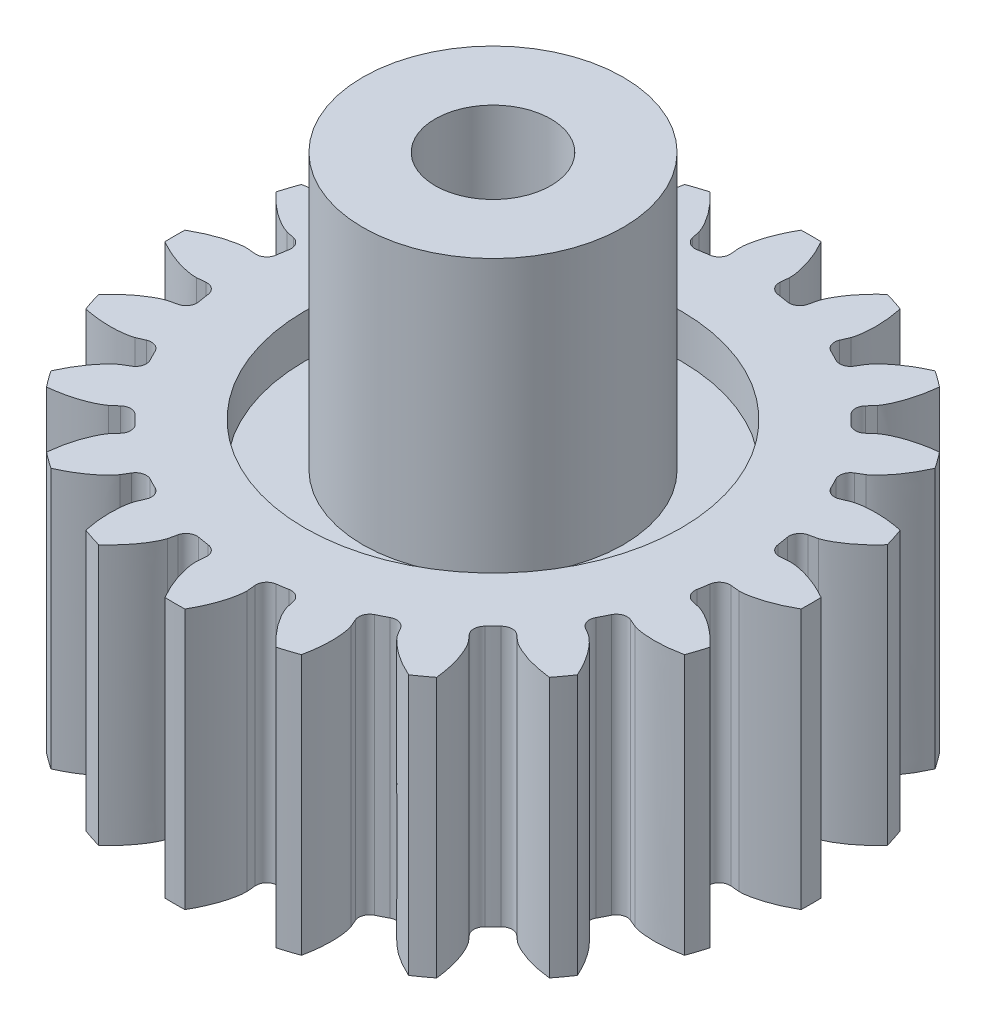
SolidWorks part; units mm, degrees
ref_plane "Front Plane" through (0, 0, 0) normal (0, 0, 1) x (1, 0, 0)
ref_plane "Top Plane" through (0, 0, 0) normal (0, 1, 0) x (1, 0, 0)
ref_plane "Right Plane" through (0, 0, 0) normal (1, 0, 0) x (0, 0, -1)
sketch "Sketch1" plane through (0, 0, 9) normal (0, -1, 0) x (1, 0, 0)
  line L0 (9.0775, -9.8507) -> (9.3734, -9.8777)
  line L1 (9.3734, -8.1223) -> (9.0775, -8.1493)
  line L2 (8.8961, -7.004) -> (9.1858, -6.9382)
  line L3 (8.6434, -5.2687) -> (8.3703, -5.3858)
  line L4 (7.8439, -4.3526) -> (8.0991, -4.2006)
  line L5 (7.0673, -2.7804) -> (6.8438, -2.9761)
  line L6 (6.0239, -2.1562) -> (6.2196, -1.9327)
  line L7 (4.7994, -0.9009) -> (4.6474, -1.1561)
  line L8 (3.6142, -0.6297) -> (3.7313, -0.3566)
  line L9 (2.0618, 0.1858) -> (1.996, -0.1039)
  line L10 (0.8507, 0.0775) -> (0.8777, 0.3734)
  line L11 (-0.8777, 0.3734) -> (-0.8507, 0.0775)
  line L12 (-1.996, -0.1039) -> (-2.0618, 0.1858)
  line L13 (-3.7313, -0.3566) -> (-3.6142, -0.6297)
  line L14 (-4.6474, -1.1561) -> (-4.7994, -0.9009)
  line L15 (-6.2196, -1.9327) -> (-6.0239, -2.1562)
  line L16 (-6.8438, -2.9761) -> (-7.0673, -2.7804)
  line L17 (-8.0991, -4.2006) -> (-7.8439, -4.3526)
  line L18 (-8.3703, -5.3858) -> (-8.6434, -5.2687)
  line L19 (-9.1858, -6.9382) -> (-8.8961, -7.004)
  line L20 (-9.0775, -8.1493) -> (-9.3734, -8.1223)
  line L21 (-9.3734, -9.8777) -> (-9.0775, -9.8507)
  line L22 (-8.8961, -10.996) -> (-9.1858, -11.0618)
  line L23 (-8.6434, -12.7313) -> (-8.3703, -12.6142)
  line L24 (-7.8439, -13.6474) -> (-8.0991, -13.7994)
  line L25 (-7.0673, -15.2196) -> (-6.8438, -15.0239)
  line L26 (-6.0239, -15.8438) -> (-6.2196, -16.0673)
  line L27 (-4.7994, -17.0991) -> (-4.6474, -16.8439)
  line L28 (-3.6142, -17.3703) -> (-3.7313, -17.6434)
  line L29 (-2.0618, -18.1858) -> (-1.996, -17.8961)
  line L30 (-0.8507, -18.0775) -> (-0.8777, -18.3734)
  line L31 (0.8777, -18.3734) -> (0.8507, -18.0775)
  line L32 (1.996, -17.8961) -> (2.0618, -18.1858)
  line L33 (3.7313, -17.6434) -> (3.6142, -17.3703)
  line L34 (4.6474, -16.8439) -> (4.7994, -17.0991)
  line L35 (6.2196, -16.0673) -> (6.0239, -15.8438)
  line L36 (6.8438, -15.0239) -> (7.0673, -15.2196)
  line L37 (8.0991, -13.7994) -> (7.8439, -13.6474)
  line L38 (8.3703, -12.6142) -> (8.6434, -12.7313)
  line L39 (9.1858, -11.0618) -> (8.8961, -10.996)
  arc A0 (8.6092, -10.5634) -> (8.671, -10.1735) centre (0, -9) ccw
  arc A1 (8.671, -10.1735) -> (9.0775, -9.8507) centre (9.0425, -10.2241) cw
  arc A2 (10.9945, -9.3464) -> (10.9945, -8.6536) centre (-0.0001, -9) ccw
  arc A3 (9.0775, -8.1493) -> (8.671, -7.8265) centre (9.0425, -7.7759) cw
  arc A4 (8.671, -7.8265) -> (8.6092, -7.4366) centre (0, -9) ccw
  arc A5 (8.6092, -7.4366) -> (8.8961, -7.004) centre (8.9782, -7.3699) cw
  arc A6 (10.5634, -5.932) -> (10.3493, -5.273) centre (-0.0001, -9) ccw
  arc A7 (8.3703, -5.3858) -> (7.8839, -5.2045) centre (8.2217, -5.0415) cw
  arc A8 (7.8839, -5.2045) -> (7.7047, -4.8527) centre (0, -9) ccw
  arc A9 (7.7047, -4.8527) -> (7.8439, -4.3526) centre (8.0351, -4.6752) cw
  arc A10 (9.0983, -2.8179) -> (8.6911, -2.2573) centre (-0.0001, -9) ccw
  arc A11 (6.8438, -2.9761) -> (6.3252, -2.954) centre (6.5961, -2.6946) cw
  arc A12 (6.3252, -2.954) -> (6.046, -2.6748) centre (0, -9) ccw
  arc A13 (6.046, -2.6748) -> (6.0239, -2.1562) centre (6.3054, -2.4039) cw
  arc A14 (6.7427, -0.3089) -> (6.1821, 0.0983) centre (0, -9.0001) ccw
  arc A15 (4.6474, -1.1561) -> (4.1473, -1.2953) centre (4.3248, -0.9649) cw
  arc A16 (4.1473, -1.2953) -> (3.7955, -1.1161) centre (0, -9) ccw
  arc A17 (3.7955, -1.1161) -> (3.6142, -0.6297) centre (3.9585, -0.7783) cw
  arc A18 (3.727, 1.3493) -> (3.068, 1.5634) centre (0, -9.0001) ccw
  arc A19 (1.996, -0.1039) -> (1.5634, -0.3908) centre (1.6301, -0.0218) cw
  arc A20 (1.5634, -0.3908) -> (1.1735, -0.329) centre (0, -9) ccw
  arc A21 (1.1735, -0.329) -> (0.8507, 0.0775) centre (1.2241, 0.0425) cw
  arc A22 (0.3464, 1.9945) -> (-0.3464, 1.9945) centre (0, -9.0001) ccw
  arc A23 (-0.8507, 0.0775) -> (-1.1735, -0.329) centre (-1.2241, 0.0425) cw
  arc A24 (-1.1735, -0.329) -> (-1.5634, -0.3908) centre (0, -9) ccw
  arc A25 (-1.5634, -0.3908) -> (-1.996, -0.1039) centre (-1.6301, -0.0218) cw
  arc A26 (-3.068, 1.5634) -> (-3.727, 1.3493) centre (0, -9.0001) ccw
  arc A27 (-3.6142, -0.6297) -> (-3.7955, -1.1161) centre (-3.9585, -0.7783) cw
  arc A28 (-3.7955, -1.1161) -> (-4.1473, -1.2953) centre (0, -9) ccw
  arc A29 (-4.1473, -1.2953) -> (-4.6474, -1.1561) centre (-4.3248, -0.9649) cw
  arc A30 (-6.1821, 0.0983) -> (-6.7427, -0.3089) centre (0, -9.0001) ccw
  arc A31 (-6.0239, -2.1562) -> (-6.046, -2.6748) centre (-6.3054, -2.4039) cw
  arc A32 (-6.046, -2.6748) -> (-6.3252, -2.954) centre (0, -9) ccw
  arc A33 (-6.3252, -2.954) -> (-6.8438, -2.9761) centre (-6.5961, -2.6946) cw
  arc A34 (-8.6911, -2.2573) -> (-9.0983, -2.8179) centre (0.0001, -9) ccw
  arc A35 (-7.8439, -4.3526) -> (-7.7047, -4.8527) centre (-8.0351, -4.6752) cw
  arc A36 (-7.7047, -4.8527) -> (-7.8839, -5.2045) centre (0, -9) ccw
  arc A37 (-7.8839, -5.2045) -> (-8.3703, -5.3858) centre (-8.2217, -5.0415) cw
  arc A38 (-10.3493, -5.273) -> (-10.5634, -5.932) centre (0.0001, -9) ccw
  arc A39 (-8.8961, -7.004) -> (-8.6092, -7.4366) centre (-8.9782, -7.3699) cw
  arc A40 (-8.6092, -7.4366) -> (-8.671, -7.8265) centre (0, -9) ccw
  arc A41 (-8.671, -7.8265) -> (-9.0775, -8.1493) centre (-9.0425, -7.7759) cw
  arc A42 (-10.9945, -8.6536) -> (-10.9945, -9.3464) centre (0.0001, -9) ccw
  arc A43 (-9.0775, -9.8507) -> (-8.671, -10.1735) centre (-9.0425, -10.2241) cw
  arc A44 (-8.671, -10.1735) -> (-8.6092, -10.5634) centre (0, -9) ccw
  arc A45 (-8.6092, -10.5634) -> (-8.8961, -10.996) centre (-8.9782, -10.6301) cw
  arc A46 (-10.5634, -12.068) -> (-10.3493, -12.727) centre (0.0001, -9) ccw
  arc A47 (-8.3703, -12.6142) -> (-7.8839, -12.7955) centre (-8.2217, -12.9585) cw
  arc A48 (-7.8839, -12.7955) -> (-7.7047, -13.1473) centre (0, -9) ccw
  arc A49 (-7.7047, -13.1473) -> (-7.8439, -13.6474) centre (-8.0351, -13.3248) cw
  arc A50 (-9.0983, -15.1821) -> (-8.6911, -15.7427) centre (0.0001, -9) ccw
  arc A51 (-6.8438, -15.0239) -> (-6.3252, -15.046) centre (-6.5961, -15.3054) cw
  arc A52 (-6.3252, -15.046) -> (-6.046, -15.3252) centre (0, -9) ccw
  arc A53 (-6.046, -15.3252) -> (-6.0239, -15.8438) centre (-6.3054, -15.5961) cw
  arc A54 (-6.7427, -17.6911) -> (-6.1821, -18.0983) centre (0, -8.9999) ccw
  arc A55 (-4.6474, -16.8439) -> (-4.1473, -16.7047) centre (-4.3248, -17.0351) cw
  arc A56 (-4.1473, -16.7047) -> (-3.7955, -16.8839) centre (0, -9) ccw
  arc A57 (-3.7955, -16.8839) -> (-3.6142, -17.3703) centre (-3.9585, -17.2217) cw
  arc A58 (-3.727, -19.3493) -> (-3.068, -19.5634) centre (0, -8.9999) ccw
  arc A59 (-1.996, -17.8961) -> (-1.5634, -17.6092) centre (-1.6301, -17.9782) cw
  arc A60 (-1.5634, -17.6092) -> (-1.1735, -17.671) centre (0, -9) ccw
  arc A61 (-1.1735, -17.671) -> (-0.8507, -18.0775) centre (-1.2241, -18.0425) cw
  arc A62 (-0.3464, -19.9945) -> (0.3464, -19.9945) centre (0, -8.9999) ccw
  arc A63 (0.8507, -18.0775) -> (1.1735, -17.671) centre (1.2241, -18.0425) cw
  arc A64 (1.1735, -17.671) -> (1.5634, -17.6092) centre (0, -9) ccw
  arc A65 (1.5634, -17.6092) -> (1.996, -17.8961) centre (1.6301, -17.9782) cw
  arc A66 (3.068, -19.5634) -> (3.727, -19.3493) centre (0, -8.9999) ccw
  arc A67 (3.6142, -17.3703) -> (3.7955, -16.8839) centre (3.9585, -17.2217) cw
  arc A68 (3.7955, -16.8839) -> (4.1473, -16.7047) centre (0, -9) ccw
  arc A69 (4.1473, -16.7047) -> (4.6474, -16.8439) centre (4.3248, -17.0351) cw
  arc A70 (6.1821, -18.0983) -> (6.7427, -17.6911) centre (0, -8.9999) ccw
  arc A71 (6.0239, -15.8438) -> (6.046, -15.3252) centre (6.3054, -15.5961) cw
  arc A72 (6.046, -15.3252) -> (6.3252, -15.046) centre (0, -9) ccw
  arc A73 (6.3252, -15.046) -> (6.8438, -15.0239) centre (6.5961, -15.3054) cw
  arc A74 (8.6911, -15.7427) -> (9.0983, -15.1821) centre (-0.0001, -9) ccw
  arc A75 (7.8439, -13.6474) -> (7.7047, -13.1473) centre (8.0351, -13.3248) cw
  arc A76 (7.7047, -13.1473) -> (7.8839, -12.7955) centre (0, -9) ccw
  arc A77 (7.8839, -12.7955) -> (8.3703, -12.6142) centre (8.2217, -12.9585) cw
  arc A78 (10.3493, -12.727) -> (10.5634, -12.068) centre (-0.0001, -9) ccw
  arc A79 (8.8961, -10.996) -> (8.6092, -10.5634) centre (8.9782, -10.6301) cw
  spline S0 degree 3 poles (9.3734, -9.8777) (9.5088, -9.8801) (9.6445, -9.8584) (9.7771, -9.8308) (9.9887, -9.7868) (10.1959, -9.7199) (10.3963, -9.6391) (10.6021, -9.556) (10.802, -9.4571) (10.9945, -9.3464) knots 0 0 0 0 0.000406 0.000406 0.000406 0.001055 0.001055 0.001055 0.001721 0.001721 0.001721 0.001721
  spline S1 degree 3 poles (10.9945, -8.6536) (10.7523, -8.5143) (10.4979, -8.3933) (10.2347, -8.2995) (10.0978, -8.2507) (9.9579, -8.2091) (9.8159, -8.1775) (9.6708, -8.1453) (9.522, -8.1197) (9.3734, -8.1223) knots 0 0 0 0 0.000838 0.000838 0.000838 0.001273 0.001273 0.001273 0.001719 0.001719 0.001719 0.001719
  spline S2 degree 3 poles (9.1858, -6.9382) (9.3154, -6.8986) (9.4377, -6.8361) (9.5554, -6.7689) (9.7429, -6.6616) (9.9194, -6.534) (10.085, -6.3952) (10.255, -6.2525) (10.4146, -6.0967) (10.5634, -5.932) knots 0 0 0 0 0.000406 0.000406 0.000406 0.001055 0.001055 0.001055 0.001721 0.001721 0.001721 0.001721
  spline S3 degree 3 poles (10.3493, -5.273) (10.0759, -5.2154) (9.7966, -5.179) (9.5174, -5.1711) (9.372, -5.167) (9.2261, -5.1706) (9.0814, -5.1845) (8.9334, -5.1987) (8.7839, -5.2203) (8.6434, -5.2687) knots 0 0 0 0 0.000838 0.000838 0.000838 0.001273 0.001273 0.001273 0.001719 0.001719 0.001719 0.001719
  spline S4 degree 3 poles (8.0991, -4.2006) (8.2101, -4.1229) (8.3071, -4.0256) (8.3982, -3.9253) (8.5435, -3.7654) (8.6719, -3.5894) (8.7864, -3.4062) (8.9041, -3.218) (9.0077, -3.0205) (9.0983, -2.8179) knots 0 0 0 0 0.000406 0.000406 0.000406 0.001055 0.001055 0.001055 0.001721 0.001721 0.001721 0.001721
  spline S5 degree 3 poles (8.6911, -2.2573) (8.4133, -2.287) (8.1364, -2.3386) (7.8684, -2.4175) (7.7289, -2.4585) (7.5912, -2.507) (7.4578, -2.5649) (7.3215, -2.6242) (7.186, -2.6909) (7.0673, -2.7804) knots 0 0 0 0 0.000838 0.000838 0.000838 0.001273 0.001273 0.001273 0.001719 0.001719 0.001719 0.001719
  spline S6 degree 3 poles (6.2196, -1.9327) (6.3012, -1.8245) (6.3634, -1.702) (6.419, -1.5785) (6.5077, -1.3815) (6.5755, -1.1745) (6.6278, -0.9649) (6.6816, -0.7495) (6.7191, -0.5296) (6.7427, -0.3089) knots 0 0 0 0 0.000406 0.000406 0.000406 0.001055 0.001055 0.001055 0.001721 0.001721 0.001721 0.001721
  spline S7 degree 3 poles (6.1821, 0.0983) (5.9271, -0.0157) (5.6797, -0.1504) (5.4491, -0.3082) (5.3291, -0.3903) (5.2132, -0.479) (5.1043, -0.5753) (4.9929, -0.6738) (4.8847, -0.7791) (4.7994, -0.9009) knots 0 0 0 0 0.000838 0.000838 0.000838 0.001273 0.001273 0.001273 0.001719 0.001719 0.001719 0.001719
  spline S8 degree 3 poles (3.7313, -0.3566) (3.7754, -0.2285) (3.7967, -0.0928) (3.8115, 0.0419) (3.835, 0.2566) (3.8354, 0.4744) (3.8204, 0.69) (3.805, 0.9114) (3.7727, 1.1321) (3.727, 1.3493) knots 0 0 0 0 0.000406 0.000406 0.000406 0.001055 0.001055 0.001055 0.001721 0.001721 0.001721 0.001721
  spline S9 degree 3 poles (3.068, 1.5634) (2.8607, 1.3761) (2.667, 1.1716) (2.4965, 0.9503) (2.4078, 0.8351) (2.3249, 0.7149) (2.2511, 0.5897) (2.1756, 0.4616) (2.1052, 0.328) (2.0618, 0.1858) knots 0 0 0 0 0.000838 0.000838 0.000838 0.001273 0.001273 0.001273 0.001719 0.001719 0.001719 0.001719
  spline S10 degree 3 poles (0.8777, 0.3734) (0.8801, 0.5088) (0.8584, 0.6445) (0.8308, 0.7771) (0.7868, 0.9887) (0.7199, 1.1959) (0.6391, 1.3963) (0.556, 1.6021) (0.4571, 1.802) (0.3464, 1.9945) knots 0 0 0 0 0.000406 0.000406 0.000406 0.001055 0.001055 0.001055 0.001721 0.001721 0.001721 0.001721
  spline S11 degree 3 poles (-0.3464, 1.9945) (-0.4857, 1.7523) (-0.6067, 1.4979) (-0.7005, 1.2347) (-0.7493, 1.0978) (-0.7909, 0.9579) (-0.8225, 0.8159) (-0.8547, 0.6708) (-0.8803, 0.522) (-0.8777, 0.3734) knots 0 0 0 0 0.000838 0.000838 0.000838 0.001273 0.001273 0.001273 0.001719 0.001719 0.001719 0.001719
  spline S12 degree 3 poles (-2.0618, 0.1858) (-2.1014, 0.3154) (-2.1639, 0.4377) (-2.2311, 0.5554) (-2.3384, 0.7429) (-2.466, 0.9194) (-2.6048, 1.085) (-2.7475, 1.255) (-2.9033, 1.4146) (-3.068, 1.5634) knots 0 0 0 0 0.000406 0.000406 0.000406 0.001055 0.001055 0.001055 0.001721 0.001721 0.001721 0.001721
  spline S13 degree 3 poles (-3.727, 1.3493) (-3.7846, 1.0759) (-3.821, 0.7966) (-3.8289, 0.5174) (-3.833, 0.372) (-3.8294, 0.2261) (-3.8155, 0.0814) (-3.8013, -0.0666) (-3.7797, -0.2161) (-3.7313, -0.3566) knots 0 0 0 0 0.000838 0.000838 0.000838 0.001273 0.001273 0.001273 0.001719 0.001719 0.001719 0.001719
  spline S14 degree 3 poles (-4.7994, -0.9009) (-4.8771, -0.7899) (-4.9744, -0.6929) (-5.0747, -0.6018) (-5.2346, -0.4565) (-5.4106, -0.3281) (-5.5938, -0.2136) (-5.782, -0.0959) (-5.9795, 0.0077) (-6.1821, 0.0983) knots 0 0 0 0 0.000406 0.000406 0.000406 0.001055 0.001055 0.001055 0.001721 0.001721 0.001721 0.001721
  spline S15 degree 3 poles (-6.7427, -0.3089) (-6.713, -0.5867) (-6.6614, -0.8636) (-6.5825, -1.1316) (-6.5415, -1.2711) (-6.493, -1.4088) (-6.4351, -1.5422) (-6.3758, -1.6785) (-6.3091, -1.814) (-6.2196, -1.9327) knots 0 0 0 0 0.000838 0.000838 0.000838 0.001273 0.001273 0.001273 0.001719 0.001719 0.001719 0.001719
  spline S16 degree 3 poles (-7.0673, -2.7804) (-7.1755, -2.6988) (-7.298, -2.6366) (-7.4215, -2.581) (-7.6185, -2.4923) (-7.8255, -2.4245) (-8.0351, -2.3722) (-8.2505, -2.3184) (-8.4704, -2.2809) (-8.6911, -2.2573) knots 0 0 0 0 0.000406 0.000406 0.000406 0.001055 0.001055 0.001055 0.001721 0.001721 0.001721 0.001721
  spline S17 degree 3 poles (-9.0983, -2.8179) (-8.9843, -3.0729) (-8.8496, -3.3203) (-8.6918, -3.5509) (-8.6097, -3.6709) (-8.521, -3.7868) (-8.4247, -3.8957) (-8.3262, -4.0071) (-8.2209, -4.1153) (-8.0991, -4.2006) knots 0 0 0 0 0.000838 0.000838 0.000838 0.001273 0.001273 0.001273 0.001719 0.001719 0.001719 0.001719
  spline S18 degree 3 poles (-8.6434, -5.2687) (-8.7715, -5.2246) (-8.9072, -5.2033) (-9.0419, -5.1885) (-9.2566, -5.165) (-9.4744, -5.1646) (-9.69, -5.1796) (-9.9114, -5.195) (-10.1321, -5.2273) (-10.3493, -5.273) knots 0 0 0 0 0.000406 0.000406 0.000406 0.001055 0.001055 0.001055 0.001721 0.001721 0.001721 0.001721
  spline S19 degree 3 poles (-10.5634, -5.932) (-10.3761, -6.1393) (-10.1716, -6.333) (-9.9503, -6.5035) (-9.8351, -6.5922) (-9.7149, -6.6751) (-9.5897, -6.7489) (-9.4616, -6.8244) (-9.328, -6.8948) (-9.1858, -6.9382) knots 0 0 0 0 0.000838 0.000838 0.000838 0.001273 0.001273 0.001273 0.001719 0.001719 0.001719 0.001719
  spline S20 degree 3 poles (-9.3734, -8.1223) (-9.5088, -8.1199) (-9.6445, -8.1416) (-9.7771, -8.1692) (-9.9887, -8.2132) (-10.1959, -8.2801) (-10.3963, -8.3609) (-10.6021, -8.444) (-10.802, -8.5429) (-10.9945, -8.6536) knots 0 0 0 0 0.000406 0.000406 0.000406 0.001055 0.001055 0.001055 0.001721 0.001721 0.001721 0.001721
  spline S21 degree 3 poles (-10.9945, -9.3464) (-10.7523, -9.4857) (-10.4979, -9.6067) (-10.2347, -9.7005) (-10.0978, -9.7493) (-9.9579, -9.7909) (-9.8159, -9.8225) (-9.6708, -9.8547) (-9.522, -9.8803) (-9.3734, -9.8777) knots 0 0 0 0 0.000838 0.000838 0.000838 0.001273 0.001273 0.001273 0.001719 0.001719 0.001719 0.001719
  spline S22 degree 3 poles (-9.1858, -11.0618) (-9.3154, -11.1014) (-9.4377, -11.1639) (-9.5554, -11.2311) (-9.7429, -11.3384) (-9.9194, -11.466) (-10.085, -11.6048) (-10.255, -11.7475) (-10.4146, -11.9033) (-10.5634, -12.068) knots 0 0 0 0 0.000406 0.000406 0.000406 0.001055 0.001055 0.001055 0.001721 0.001721 0.001721 0.001721
  spline S23 degree 3 poles (-10.3493, -12.727) (-10.0759, -12.7846) (-9.7966, -12.821) (-9.5174, -12.8289) (-9.372, -12.833) (-9.2261, -12.8294) (-9.0814, -12.8155) (-8.9334, -12.8013) (-8.7839, -12.7797) (-8.6434, -12.7313) knots 0 0 0 0 0.000838 0.000838 0.000838 0.001273 0.001273 0.001273 0.001719 0.001719 0.001719 0.001719
  spline S24 degree 3 poles (-8.0991, -13.7994) (-8.2101, -13.8771) (-8.3071, -13.9744) (-8.3982, -14.0747) (-8.5435, -14.2346) (-8.6719, -14.4106) (-8.7864, -14.5938) (-8.9041, -14.782) (-9.0077, -14.9795) (-9.0983, -15.1821) knots 0 0 0 0 0.000406 0.000406 0.000406 0.001055 0.001055 0.001055 0.001721 0.001721 0.001721 0.001721
  spline S25 degree 3 poles (-8.6911, -15.7427) (-8.4133, -15.713) (-8.1364, -15.6614) (-7.8684, -15.5825) (-7.7289, -15.5415) (-7.5912, -15.493) (-7.4578, -15.4351) (-7.3215, -15.3758) (-7.186, -15.3091) (-7.0673, -15.2196) knots 0 0 0 0 0.000838 0.000838 0.000838 0.001273 0.001273 0.001273 0.001719 0.001719 0.001719 0.001719
  spline S26 degree 3 poles (-6.2196, -16.0673) (-6.3012, -16.1755) (-6.3634, -16.298) (-6.419, -16.4215) (-6.5077, -16.6185) (-6.5755, -16.8255) (-6.6278, -17.0351) (-6.6816, -17.2505) (-6.7191, -17.4704) (-6.7427, -17.6911) knots 0 0 0 0 0.000406 0.000406 0.000406 0.001055 0.001055 0.001055 0.001721 0.001721 0.001721 0.001721
  spline S27 degree 3 poles (-6.1821, -18.0983) (-5.9271, -17.9843) (-5.6797, -17.8496) (-5.4491, -17.6918) (-5.3291, -17.6097) (-5.2132, -17.521) (-5.1043, -17.4247) (-4.9929, -17.3262) (-4.8847, -17.2209) (-4.7994, -17.0991) knots 0 0 0 0 0.000838 0.000838 0.000838 0.001273 0.001273 0.001273 0.001719 0.001719 0.001719 0.001719
  spline S28 degree 3 poles (-3.7313, -17.6434) (-3.7754, -17.7715) (-3.7967, -17.9072) (-3.8115, -18.0419) (-3.835, -18.2566) (-3.8354, -18.4744) (-3.8204, -18.69) (-3.805, -18.9114) (-3.7727, -19.1321) (-3.727, -19.3493) knots 0 0 0 0 0.000406 0.000406 0.000406 0.001055 0.001055 0.001055 0.001721 0.001721 0.001721 0.001721
  spline S29 degree 3 poles (-3.068, -19.5634) (-2.8607, -19.3761) (-2.667, -19.1716) (-2.4965, -18.9503) (-2.4078, -18.8351) (-2.3249, -18.7149) (-2.2511, -18.5897) (-2.1756, -18.4616) (-2.1052, -18.328) (-2.0618, -18.1858) knots 0 0 0 0 0.000838 0.000838 0.000838 0.001273 0.001273 0.001273 0.001719 0.001719 0.001719 0.001719
  spline S30 degree 3 poles (-0.8777, -18.3734) (-0.8801, -18.5088) (-0.8584, -18.6445) (-0.8308, -18.7771) (-0.7868, -18.9887) (-0.7199, -19.1959) (-0.6391, -19.3963) (-0.556, -19.6021) (-0.4571, -19.802) (-0.3464, -19.9945) knots 0 0 0 0 0.000406 0.000406 0.000406 0.001055 0.001055 0.001055 0.001721 0.001721 0.001721 0.001721
  spline S31 degree 3 poles (0.3464, -19.9945) (0.4857, -19.7523) (0.6067, -19.4979) (0.7005, -19.2347) (0.7493, -19.0978) (0.7909, -18.9579) (0.8225, -18.8159) (0.8547, -18.6708) (0.8803, -18.522) (0.8777, -18.3734) knots 0 0 0 0 0.000838 0.000838 0.000838 0.001273 0.001273 0.001273 0.001719 0.001719 0.001719 0.001719
  spline S32 degree 3 poles (2.0618, -18.1858) (2.1014, -18.3154) (2.1639, -18.4377) (2.2311, -18.5554) (2.3384, -18.7429) (2.466, -18.9194) (2.6048, -19.085) (2.7475, -19.255) (2.9033, -19.4146) (3.068, -19.5634) knots 0 0 0 0 0.000406 0.000406 0.000406 0.001055 0.001055 0.001055 0.001721 0.001721 0.001721 0.001721
  spline S33 degree 3 poles (3.727, -19.3493) (3.7846, -19.0759) (3.821, -18.7966) (3.8289, -18.5174) (3.833, -18.372) (3.8294, -18.2261) (3.8155, -18.0814) (3.8013, -17.9334) (3.7797, -17.7839) (3.7313, -17.6434) knots 0 0 0 0 0.000838 0.000838 0.000838 0.001273 0.001273 0.001273 0.001719 0.001719 0.001719 0.001719
  spline S34 degree 3 poles (4.7994, -17.0991) (4.8771, -17.2101) (4.9744, -17.3071) (5.0747, -17.3982) (5.2346, -17.5435) (5.4106, -17.6719) (5.5938, -17.7864) (5.782, -17.9041) (5.9795, -18.0077) (6.1821, -18.0983) knots 0 0 0 0 0.000406 0.000406 0.000406 0.001055 0.001055 0.001055 0.001721 0.001721 0.001721 0.001721
  spline S35 degree 3 poles (6.7427, -17.6911) (6.713, -17.4133) (6.6614, -17.1364) (6.5825, -16.8684) (6.5415, -16.7289) (6.493, -16.5912) (6.4351, -16.4578) (6.3758, -16.3215) (6.3091, -16.186) (6.2196, -16.0673) knots 0 0 0 0 0.000838 0.000838 0.000838 0.001273 0.001273 0.001273 0.001719 0.001719 0.001719 0.001719
  spline S36 degree 3 poles (7.0673, -15.2196) (7.1755, -15.3012) (7.298, -15.3634) (7.4215, -15.419) (7.6185, -15.5077) (7.8255, -15.5755) (8.0351, -15.6278) (8.2505, -15.6816) (8.4704, -15.7191) (8.6911, -15.7427) knots 0 0 0 0 0.000406 0.000406 0.000406 0.001055 0.001055 0.001055 0.001721 0.001721 0.001721 0.001721
  spline S37 degree 3 poles (9.0983, -15.1821) (8.9843, -14.9271) (8.8496, -14.6797) (8.6918, -14.4491) (8.6097, -14.3291) (8.521, -14.2132) (8.4247, -14.1043) (8.3262, -13.9929) (8.2209, -13.8847) (8.0991, -13.7994) knots 0 0 0 0 0.000838 0.000838 0.000838 0.001273 0.001273 0.001273 0.001719 0.001719 0.001719 0.001719
  spline S38 degree 3 poles (8.6434, -12.7313) (8.7715, -12.7754) (8.9072, -12.7967) (9.0419, -12.8115) (9.2566, -12.835) (9.4744, -12.8354) (9.69, -12.8204) (9.9114, -12.805) (10.1321, -12.7727) (10.3493, -12.727) knots 0 0 0 0 0.000406 0.000406 0.000406 0.001055 0.001055 0.001055 0.001721 0.001721 0.001721 0.001721
  spline S39 degree 3 poles (10.5634, -12.068) (10.3761, -11.8607) (10.1716, -11.667) (9.9503, -11.4965) (9.8351, -11.4078) (9.7149, -11.3249) (9.5897, -11.2511) (9.4616, -11.1756) (9.328, -11.1052) (9.1858, -11.0618) knots 0 0 0 0 0.000838 0.000838 0.000838 0.001273 0.001273 0.001273 0.001719 0.001719 0.001719 0.001719
extrude "Boss-Extrude1" add sketch "Sketch1" against normal blind 4.5 and the other way blind 4.5
sketch "Sketch3" plane through (0, 4.5, 0) normal (0, 1, 0) x (1, 0, 0)
  circle A0 centre (0, 0) radius 4.5
  dimension "D1" = 9
extrude "Boss-Extrude2" add sketch "Sketch3" along normal blind 8
sketch "Sketch4" plane through (0, 4.5, 0) normal (0, 1, 0) x (1, 0, 0)
  circle A0 centre (0, 0) radius 6.5
  circle A1 centre (0, 0) radius 4.5 construction
  circle A2 centre (0, 0) radius 4.5
  dimension "D1" = 13
extrude "Cut-Extrude1" cut sketch "Sketch4" against normal blind 1.5
sketch "Sketch5" plane through (0, -4.5, 0) normal (0, -1, 0) x (1, 0, 0)
  circle A0 centre (0, 0) radius 4.5 construction
  circle A1 centre (0, 0) radius 6.5 construction
  circle A2 centre (0, 0) radius 4.5
  circle A3 centre (0, 0) radius 6.5
extrude "Cut-Extrude2" cut sketch "Sketch5" against normal blind 1.5
sketch "Sketch6" plane through (0, 12.5, 0) normal (0, 1, 0) x (1, 0, 0)
  circle A0 centre (0, 0) radius 2
  dimension "D1" = 4
extrude "Cut-Extrude3" cut sketch "Sketch6" against normal up to next
